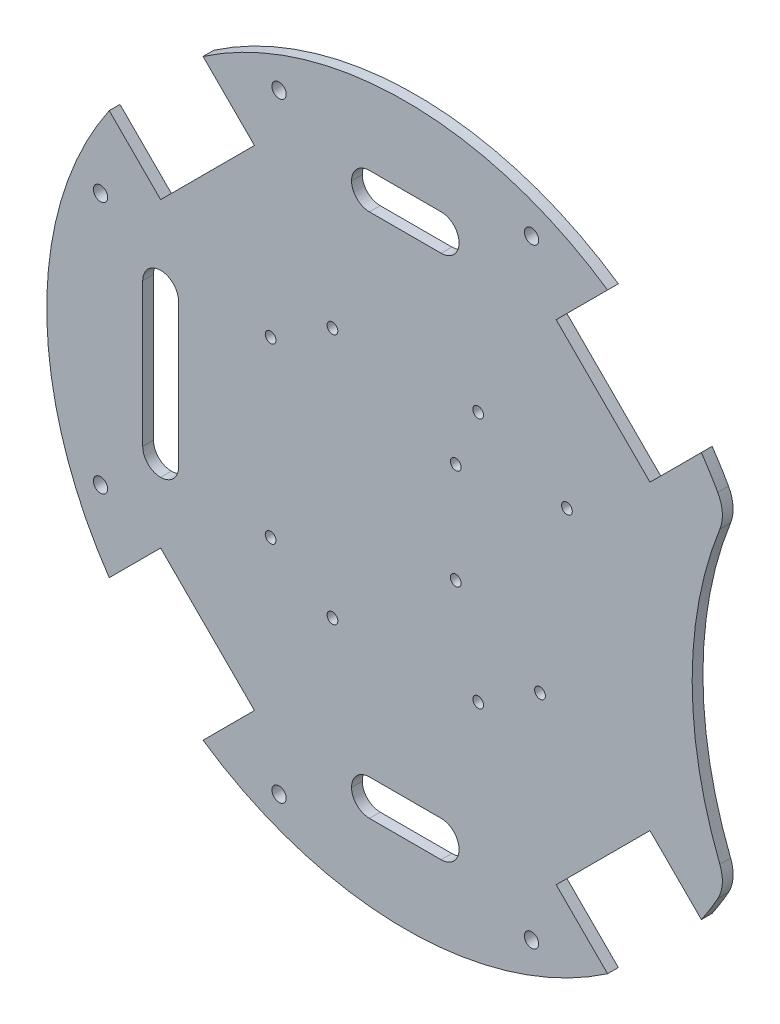
SolidWorks part; units mm, degrees
ref_plane "Alzado" through (0, 0, 0) normal (0, 0, 1) x (1, 0, 0)
ref_plane "Planta" through (0, 0, 0) normal (0, 1, 0) x (1, 0, 0)
ref_plane "Vista lateral" through (0, 0, 0) normal (1, 0, 0) x (0, 0, -1)
sketch "Croquis1" plane through (0, 0, 0) normal (0, 0, 1) x (1, 0, 0)
  circle A0 centre (0, 0) radius 100
  dimension "D1" = 200
extrude "Saliente-Extruir1" add sketch "Croquis1" along normal blind 3
sketch "Croquis3" plane through (0, 0, 3) normal (0, 0, 1) x (1, 0, 0)
  line L0 (0, 0) -> (190, 0) construction
  circle A0 centre (190, 0) radius 110
  dimension "D1" = 220
  dimension "D2" = 190
extrude "Cortar-Extruir1" cut sketch "Croquis3" against normal blind 3
fillet "Redondeo1" radius 10 2 edges at (89.4737, -44.6594, 1.5) (89.4737, 44.6594, 1.5)
sketch "Croquis4" plane through (0, 0, 3) normal (0, 0, 1) x (1, 0, 0)
  line L0 (0, 0) -> (-70.7107, -70.7107) construction
  line L1 (-57.6292, -83.7922) -> (-83.7922, -57.6292)
  line L2 (-57.6292, 83.7922) -> (-42.0729, 68.2358)
  line L3 (-83.7922, -57.6292) -> (-68.2358, -42.0729)
  line L4 (-68.2358, -42.0729) -> (-42.0729, -68.2358)
  line L5 (-42.0729, -68.2358) -> (-57.6292, -83.7922)
  line L6 (-42.0729, 68.2358) -> (-68.2358, 42.0729)
  line L7 (-68.2358, 42.0729) -> (-83.7922, 57.6292)
  line L8 (-83.7922, 57.6292) -> (-57.6292, 83.7922)
  line L9 (83.7922, 57.6292) -> (68.2358, 42.0729)
  line L10 (68.2358, 42.0729) -> (42.0729, 68.2358)
  line L11 (42.0729, 68.2358) -> (57.6292, 83.7922)
  line L12 (57.6292, 83.7922) -> (83.7922, 57.6292)
  line L13 (57.6292, -83.7922) -> (42.0729, -68.2358)
  line L14 (42.0729, -68.2358) -> (68.2358, -42.0729)
  line L15 (68.2358, -42.0729) -> (83.7922, -57.6292)
  line L16 (83.7922, -57.6292) -> (57.6292, -83.7922)
  arc A0 (87.1345, 49.0671) -> (87.1345, -49.0671) centre (0, 0) ccw construction
  point P25 (0, 0)
  dimension "D3" = 18.5
  dimension "D4" = 78
  dimension "D1" = 22
  dimension "D2" = 37
  dimension "D5" = 4
extrude "Cortar-Extruir2" cut sketch "Croquis4" against normal through all
sketch "Croquis6" plane through (0, 0, 3) normal (0, 0, 1) x (1, 0, 0)
  line L0 (-68.2358, -42.0729) -> (-68.1778, 42.4239) construction
  line L3 (-42.0729, -68.2358) -> (42.0729, -68.2358) construction
  line L4 (-63.2358, -25) -> (-63.2358, 25)
  line L5 (-63.2358, 0) -> (0, 0) construction
  line L6 (-63.2358, 25) -> (-73.2358, 25)
  line L7 (-73.2358, 25) -> (-73.2358, -25)
  line L8 (-73.2358, -25) -> (-63.2358, -25)
  line L12 (-15, 78.24) -> (15, 78.24)
  line L13 (-15, 68.24) -> (-15, 78.24)
  line L14 (-15, 68.24) -> (15, 68.24)
  line L15 (15, 78.24) -> (15, 68.24)
  line L19 (-15, -68.24) -> (-15, -78.24)
  line L20 (-15, -78.24) -> (15, -78.24)
  line L21 (-15, -68.24) -> (15, -68.24)
  line L22 (15, -78.24) -> (15, -68.24)
  line L23 (0, 0) -> (0, -68.24) construction
  arc A1 (-82.5716, 56.4086) -> (-82.5716, -56.4086) centre (0, 0) ccw construction
  arc A2 (-56.4086, -82.5716) -> (56.4086, -82.5716) centre (0, 0) ccw construction
  point P44 (0, 0)
  dimension "D1" = 63.2358
  dimension "D2" = 10
  dimension "D3" = 73.2358
  dimension "D4" = 50
  dimension "D5" = 25
  dimension "D6" = 68.24
  dimension "D7" = 10
  dimension "D8" = 30
  dimension "D9" = 15
  dimension "D10" = 78.24
extrude "Cortar-Extruir4" cut sketch "Croquis6" against normal blind 10
fillet "Redondeo3" radius 5 12 edges at (15, -78.24, 1.5) (-15, -78.24, 1.5) (15, -68.24, 1.5) (-15, -68.24, 1.5) (-73.2358, -25, 1.5) (-63.2358, -25, 1.5) (-73.2358, 25, 1.5) (-63.2358, 25, 1.5) (-15, 68.24, 1.5) (15, 68.24, 1.5) (-15, 78.24, 1.5) (15, 78.24, 1.5)
sketch "Croquis7" plane through (0, 0, 0) normal (0, 0, -1) x (-1, 0, 0)
  line L0 (0, 24.17) -> (0, -24.17) construction
  line L2 (37.565, -24.17) -> (-37.565, -24.17) construction
  line L4 (37.565, 24.17) -> (-45.065, 24.17) construction
  line L5 (37.565, 24.17) -> (37.565, -24.17) construction
  line L6 (-45.065, 24.17) -> (-14.0656, 19.2975) construction
  line L7 (-14.0656, 19.2975) -> (37.565, 24.17) construction
  line L8 (37.565, -24.17) -> (-14.0612, -8.7146) construction
  line L9 (-14.0612, -8.7146) -> (-37.565, -24.17) construction
  circle A0 centre (37.565, -24.17) radius 1.5
  circle A1 centre (-37.565, -24.17) radius 1.5
  circle A2 centre (-45.065, 24.17) radius 1.5
  circle A3 centre (37.565, 24.17) radius 1.5
  circle A4 centre (-14.0656, 19.2975) radius 1.5
  circle A5 centre (-14.0612, -8.7146) radius 1.5
  arc A6 (82.5716, -56.4086) -> (82.5716, 56.4086) centre (0, 0) ccw construction
  dimension "D1" = 3
  dimension "D2" = 3
  dimension "D3" = 3
  dimension "D4" = 3
  dimension "D5" = 3
  dimension "D12" = 3
  dimension "D6" = 31.38
  dimension "D7" = 82.63
  dimension "D8" = 51.86
  dimension "D9" = 75.13
  dimension "D10" = 53.89
  dimension "D11" = 28.13
  dimension "D13" = 48.34
  dimension "D14" = 37.565
extrude "Cortar-Extruir5" cut sketch "Croquis7" against normal through all
sketch "Croquis8" plane through (0, 0, 0) normal (0, 0, -1) x (-1, 0, 0)
  line L0 (0, 0) -> (0, 35) construction
  line L1 (20.32, 35) -> (-20.32, 35) construction
  line L2 (0, 0) -> (63.2358, 0) construction
  line L3 (63.2358, -20) -> (63.2358, 20) construction
  circle A0 centre (-20.32, 35) radius 1.5
  circle A1 centre (20.32, 35) radius 1.5
  circle A2 centre (20.32, -35) radius 1.5
  circle A3 centre (-20.32, -35) radius 1.5
  dimension "D1" = 3
  dimension "D2" = 3
  dimension "D3" = 40.64
  dimension "D4" = 20.32
  dimension "D5" = 35
extrude "Cortar-Extruir6" cut sketch "Croquis8" against normal through all
sketch "Croquis9" plane through (0, 0, 0) normal (0, 0, -1) x (-1, 0, 0)
  line L0 (-56.4086, 82.5716) -> (-42.0729, 68.2358) construction
  line L2 (-38.2683, 92.388) -> (-35.2069, 84.9969) construction
  arc A0 (56.4086, 82.5716) -> (-56.4086, 82.5716) centre (0, 0) ccw construction
  circle A1 centre (-35.2069, 84.9969) radius 2
  circle A2 centre (35.2069, 84.9969) radius 2
  circle A3 centre (84.9969, 35.2069) radius 2
  circle A4 centre (84.9969, -35.2069) radius 2
  circle A5 centre (35.2069, -84.9969) radius 2
  circle A6 centre (-35.2069, -84.9969) radius 2
  circle A9 centre (-84.9969, -35.2069) radius 2 [skipped]
  circle A10 centre (-84.9969, 35.2069) radius 2 [skipped]
  point P26 (0, 0)
  dimension "D2" = 4
  dimension "D3" = 35.2069
  dimension "D4" = 16.7069
  dimension "D1" = 8
  dimension "D5" = 8
extrude "Cortar-Extruir7" cut sketch "Croquis9" against normal through all
